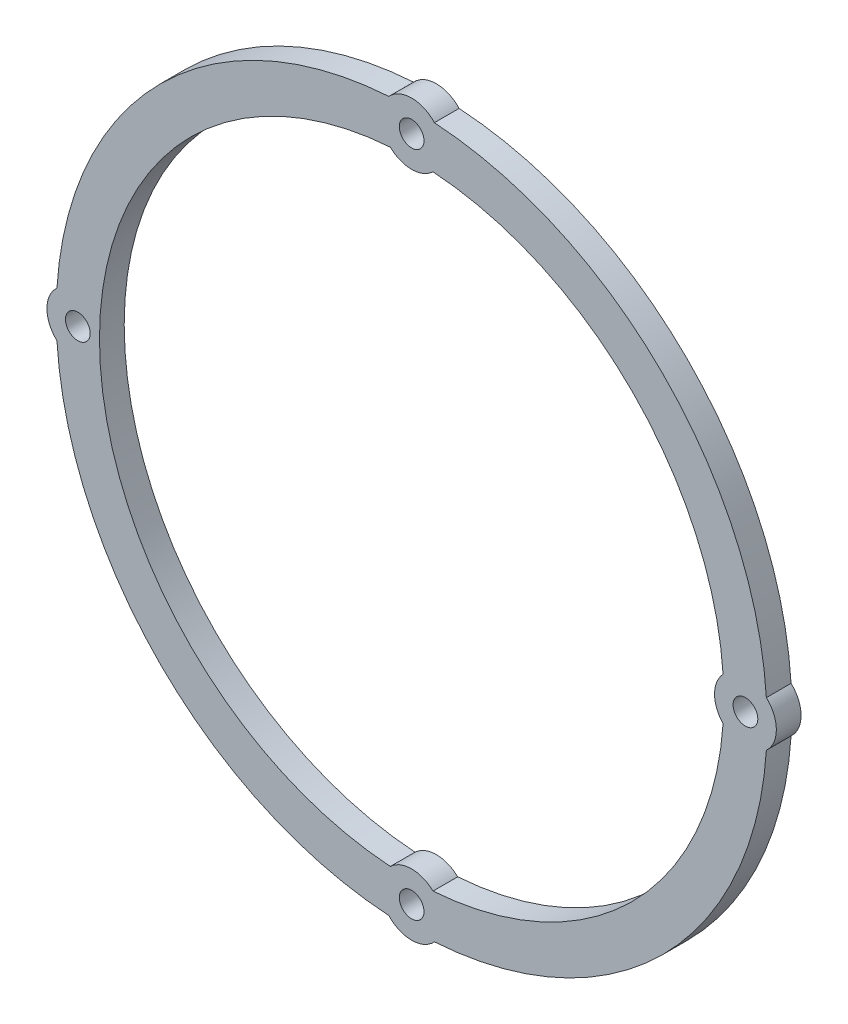
SolidWorks part; units mm, degrees
ref_plane "Alzado" through (0, 0, 0) normal (0, 0, 1) x (1, 0, 0)
ref_plane "Planta" through (0, 0, 0) normal (0, 1, 0) x (1, 0, 0)
ref_plane "Vista lateral" through (0, 0, 0) normal (1, 0, 0) x (0, 0, -1)
sketch "Croquis1" plane through (0, 0, 0) normal (0, 0, 1) x (1, 0, 0)
  circle A0 centre (0, 0) radius 57.5
  circle A1 centre (0, 0) radius 54 construction
  circle A2 centre (0, 54) radius 2
  circle A3 centre (0, 0) radius 50.5
  circle A7 centre (54, 0) radius 2
  circle A9 centre (0, -54) radius 2
  circle A11 centre (-54, 0) radius 2
  circle A12 centre (0, 54) radius 5
  circle A13 centre (54, 0) radius 5
  circle A14 centre (0, -54) radius 5
  circle A15 centre (-54, 0) radius 5
  point P10 (0, 0)
  point P25 (0, 0)
  dimension "D1" = 115
  dimension "D2" = 108
  dimension "D3" = 4
  dimension "D4" = 7
  dimension "D5" = 3
  dimension "D6" = 3
  dimension "D8" = 4
extrude "Saliente-Extruir1" add sketch "Croquis1" along normal blind 4 contours A0 A12 A3 A2 | A3 A12 | A0 A12 | A13 A0 A12 A3 | A15 A3 A12 A0 | A3 A15 A0 A11 | A0 A15 | A15 A0 A14 A3 | A3 A14 | A3 A14 A0 A9 | A0 A14 | A14 A0 A13 A3 | A0 A13 A3 A7 | A3 A13 | A0 A13 | A13 | A7 region at (57.3478, -1.8384, 0) region at (58.0852, 0, 0) region at (53.8094, 5.7595, 0) region at (40.1193, -40.1193, 0) region at (4.5447, 55.7702, 0) region at (0, 58.0852, 0) region at (49.8685, 0, 0) region at (0, -58.0852, 0) region at (0, -57.3773, 0) region at (-5.7595, 53.8094, 0) region at (0, 49.8685, 0) region at (-40.1193, -40.1193, 0) region at (0, -49.8685, 0) region at (-53.8387, 4.8746, 0) region at (-58.0852, 0, 0)
